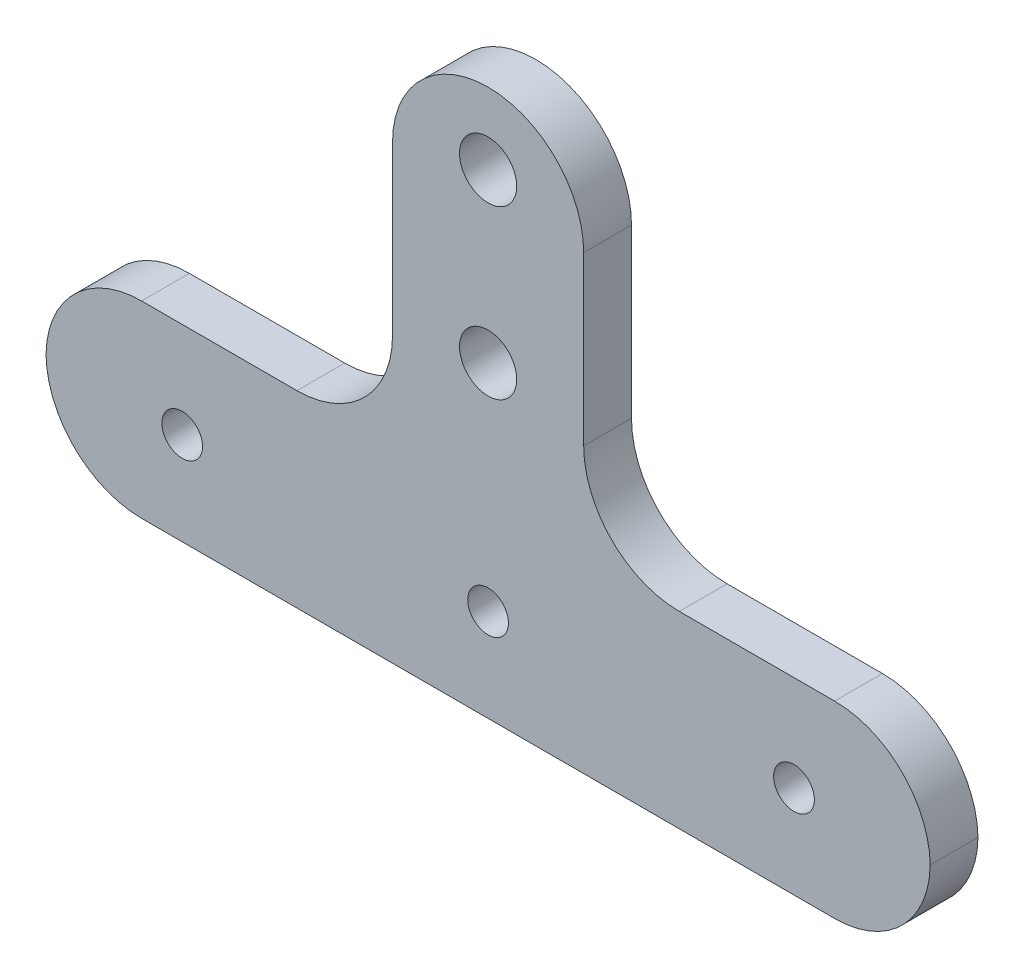
SolidWorks part; units mm, degrees
material "6061 Alloy"
ref_plane "Front Plane" through (0, 0, 0) normal (0, 0, 1) x (1, 0, 0)
ref_plane "Top Plane" through (0, 0, 0) normal (0, 1, 0) x (1, 0, 0)
ref_plane "Right Plane" through (0, 0, 0) normal (1, 0, 0) x (0, 0, -1)
sketch "Sketch1" plane through (0, 0, 0) normal (0, 0, 1) x (1, 0, 0)
  line L0 (0, 0) -> (0, 100.1403) construction
  line L1 (0, 0) -> (31.5741, 100.1403) construction
  line L2 (0, 0) -> (-31.5741, 100.1403) construction
  line L3 (-29.3687, 100.1403) -> (29.3687, 100.1403)
  line L4 (-29.3687, 100.1403) -> (-29.3687, 87.6332)
  line L5 (0, 100.1403) -> (0, 123.9528) construction
  line L6 (-29.3687, 87.6332) -> (29.3687, 87.6332)
  line L7 (31.5741, 100.1403) -> (-31.5741, 100.1403) construction
  line L8 (6.35, 117.6028) -> (6.35, 100.1403)
  line L9 (-6.35, 117.6028) -> (-6.35, 100.1403)
  line L10 (29.3687, 100.1403) -> (29.3687, 87.6332)
  circle A1 centre (0, 0) radius 105
  circle A2 centre (0, 117.6028) radius 6.35
  point P6 (0, 100.1403)
  dimension "D1" = 17.5
  dimension "D3" = 23.8125
  dimension "D4" = 210
  dimension "D5" = 58.7375
  dimension "D6" = 12.7
  dimension "D2" = 17.5
  dimension "D7" = 12.7
extrude "Body" add sketch "Sketch1" along normal blind 3.175 contours L7 L6 | L8 A1 L9 L7 | A2 L9 A1 L8 | A2 A1 region at (0, 93.8868, 0) region at (0, 102.5385, 0) region at (0, 108.9063, 0) region at (0, 117.6028, 0)
fillet "Fillet1" radius 6.35 6 edges at (6.35, 100.1403, 1.5875) (-6.35, 100.1403, 1.5875) (29.3687, 87.6332, 1.5875) (29.3687, 100.1403, 1.5875) (-29.3687, 100.1403, 1.5875) (-29.3687, 87.6332, 1.5875)
hole_wizard "#6-32 Tapped Hole1" positions "3DSketch2" profile "Sketch3" tap size "#6-32" standard "Ansi Inch" end condition through all
sketch3d "3DSketch2"
  line L1 (0, 0, 0) -> (0, 100.1403, 0) construction
  line L4 (0, 100.1403, 0) -> (0, 123.9528, 0) construction
  line L9 (20.32, 93.7903, 0) -> (-20.32, 93.7903, 0) construction
  line L21 (17.8594, 100.1403, 0) -> (-17.8594, 100.1403, 0) construction
  line L27 (12.7, 100.1403, 0) -> (23.0187, 100.1403, 0) construction
  line L28 (-23.0187, 100.1403, 0) -> (-12.7, 100.1403, 0) construction
  line L29 (0, 100.1403, 0) -> (0, 93.7903, 0) construction
  arc A3 (6.35, 117.6028, 0) -> (-6.35, 117.6028, 0) centre (0, 117.6028, 0) ccw construction
  point P0 (20.32, 93.7903, 0)
  point P2 (0, 93.7903, 0)
  point P4 (-20.32, 93.7903, 0)
  point P53 (0, 117.6028, 6.35)
  dimension "D1" = 6.35
  dimension "D3" = 40.64
sketch "Sketch3" plane through (20.32, 93.7903, 0) normal (1, 0, 0) x (0, 1, 0)
  line L0 (0, 0) -> (0, 3.175)
  line L1 (0, 3.175) -> (1.3525, 3.175)
  line L2 (1.3525, 3.175) -> (1.3525, 0)
  line L5 (1.3525, 0) -> (0, 0)
  line L11 (0, -6.35) -> (0, 107.95) construction
  dimension "Thru Tap Drill Dia." = 2.7051
  dimension "Thru Tap Drill Depth" = 3.175
cosmetic thread "Hole Thread3" parameters "D2"=3.5052
cosmetic thread "Hole Thread4" parameters "D2"=3.5052
cosmetic thread "Hole Thread5" parameters "D2"=3.5052
hole_wizard "#6 Clearance Hole2" positions "3DSketch3" profile "Sketch6" hole size "#6" standard "Ansi Inch" end condition through all
sketch3d "3DSketch3"
  line L0 (17.8594, 100.1403, 0) -> (-17.8594, 100.1403, 0) construction
  line L1 (12.7, 100.1403, 0) -> (23.0187, 100.1403, 0) construction
  line L2 (-23.0187, 100.1403, 0) -> (-12.7, 100.1403, 0) construction
  line L4 (0, 100.1403, 0) -> (0, 123.9528, 0) construction
  line L6 (6.35, 108.0778, 0) -> (-6.35, 108.0778, 0) construction
  line L7 (6.35, 117.6028, 0) -> (6.35, 106.4903, 0) construction
  line L8 (-6.35, 117.6028, 0) -> (-6.35, 106.4903, 0) construction
  line L10 (6.35, 119.1903, 0) -> (-6.35, 119.1903, 0) construction
  arc A0 (6.35, 117.6028, 0) -> (-6.35, 117.6028, 0) centre (0, 117.6028, 0) ccw construction
  point P0 (25.4317, 202.8379, 0)
  point P2 (0, 119.1903, 0)
  point P4 (0, 108.0778, 0)
  point P20 (0, 117.6028, 6.35)
  dimension "D1" = 7.9375
  dimension "D2" = 11.1125
sketch "Sketch6" plane through (0, 119.1903, 0) normal (1, 0, 0) x (0, 1, 0)
  line L0 (0, 0) -> (0, 3.175)
  line L1 (0, 3.175) -> (1.8986, 3.175)
  line L2 (1.8986, 3.175) -> (1.8986, 0)
  line L5 (1.8986, 0) -> (0, 0)
  line L11 (0, -6.35) -> (0, 107.95) construction
  dimension "Thru Hole Dia." = 3.7973
  dimension "Thru Hole Depth" = 3.175
